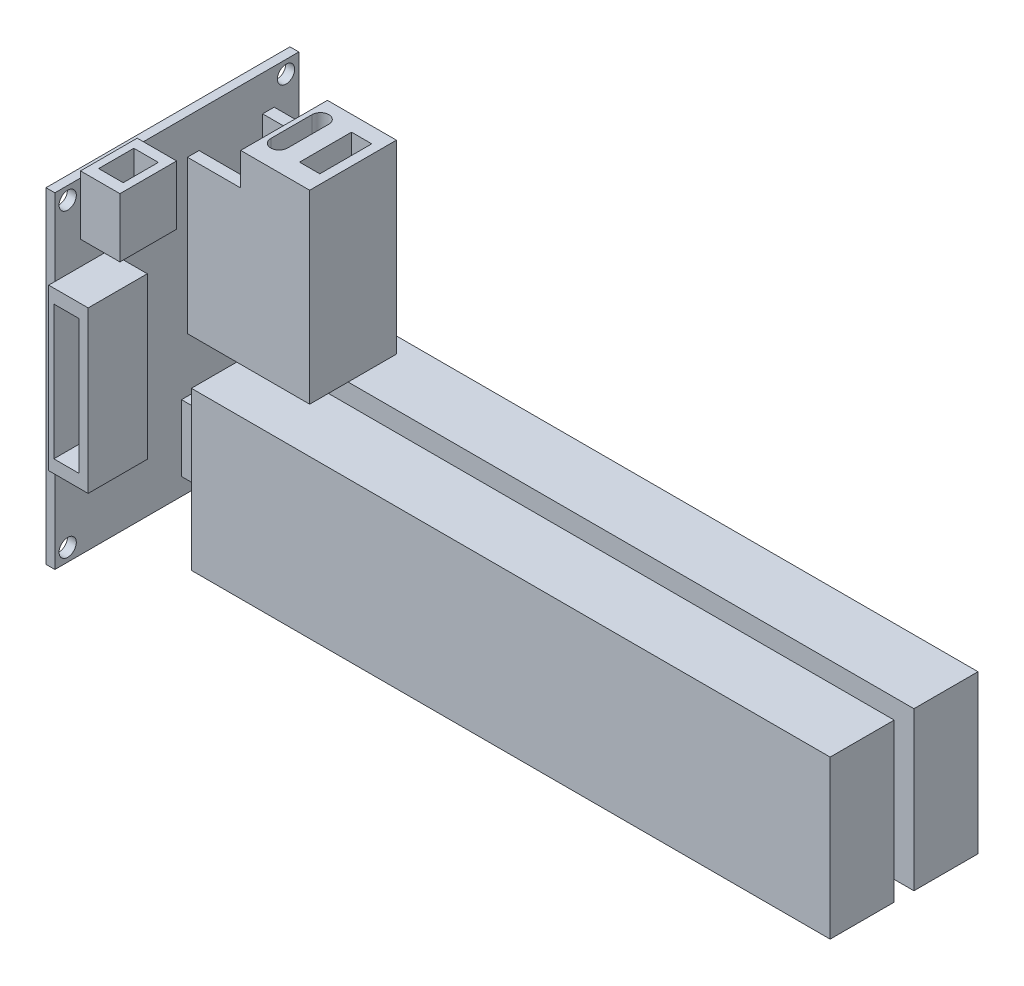
SolidWorks part; units mm, degrees
ref_plane "Płaszczyzna przednia" through (0, 0, 0) normal (0, 0, 1) x (1, 0, 0)
ref_plane "Płaszczyzna górna" through (0, 0, 0) normal (0, 1, 0) x (1, 0, 0)
ref_plane "Płaszczyzna prawa" through (0, 0, 0) normal (1, 0, 0) x (0, 0, -1)
sketch "Sketch2" plane through (0, 0, 0) normal (0, 0, 1) x (1, 0, 0)
  line L1 (0, 0) -> (129.6, 0)
  line L2 (0, 0) -> (0, 32)
  line L3 (0, 32) -> (129.6, 32)
  line L4 (129.6, 0) -> (129.6, 32)
  dimension "D1" = 32
  dimension "D2" = 129.6
extrude "Boss-Extrude1" add sketch "Sketch2" along normal blind 30
sketch "Sketch3" plane through (0, 0, 0) normal (-1, 0, 0) x (0, 0, 1)
  line L0 (0, 32) -> (0, 0) construction
  line L1 (6, 23) -> (8.4, 23)
  line L2 (6, 23) -> (6, 9.5)
  line L3 (6, 9.5) -> (8.4, 9.5)
  line L4 (8.4, 23) -> (8.4, 9.5)
  line L5 (21.6, 23) -> (24, 23)
  line L6 (21.6, 23) -> (21.6, 9.5)
  line L7 (21.6, 9.5) -> (24, 9.5)
  line L8 (24, 23) -> (24, 9.5)
  line L9 (30, 32) -> (30, 0) construction
  line L10 (30, 0) -> (0, 0) construction
  dimension "D1" = 13.5
  dimension "D2" = 2.4
  dimension "D3" = 6
  dimension "D4" = 6
  dimension "D5" = 9.5
extrude "Boss-Extrude2" add sketch "Sketch3" along normal blind 8
sketch "Sketch4" plane through (-8, 0, 0) normal (-1, 0, 0) x (0, 0, 1)
  line L1 (49.7, 6) -> (0.2, 6)
  line L2 (49.7, 6) -> (49.7, 72.2)
  line L3 (49.7, 72.2) -> (0.2, 72.2)
  line L4 (0.2, 6) -> (0.2, 72.2)
  line L5 (21.6, 9.5) -> (24, 9.5) construction
  line L6 (6, 23) -> (6, 9.5) construction
  dimension "D1" = 66.2
  dimension "D2" = 49.5
  dimension "D3" = 5.8
  dimension "D4" = 3.5
extrude "Boss-Extrude3" add sketch "Sketch4" along normal blind 1.8
sketch "Sketch5" plane through (-9.8, 0, 0) normal (-1, 0, 0) x (0, 0, 1)
  line L0 (0.2, 6) -> (49.7, 72.2) construction
  line L1 (2.8, 69.6) -> (47.1, 69.6) construction
  line L2 (2.8, 69.6) -> (2.8, 8.6) construction
  line L3 (2.8, 8.6) -> (47.1, 8.6) construction
  line L4 (47.1, 69.6) -> (47.1, 8.6) construction
  line L5 (0.2, 39.1) -> (24.95, 39.1) construction
  line L6 (0.2, 72.2) -> (0.2, 6) construction
  line L7 (2.8, 69.6) -> (47.1, 8.6) construction
  line L8 (47.1, 39.1) -> (24.95, 39.1) construction
  circle A0 centre (2.8, 69.6) radius 1.75
  circle A1 centre (47.1, 69.6) radius 1.75
  circle A2 centre (47.1, 8.6) radius 1.75
  circle A3 centre (2.8, 8.6) radius 1.75
  dimension "D1" = 2
  dimension "D3" = 3.5
  dimension "D4" = 61
  dimension "D5" = 44.3
  dimension "D2" = 2
extrude "Cut-Extrude1" cut sketch "Sketch5" against normal blind 1.8
sketch "Sketch6" plane through (-8, 0, 0) normal (1, 0, 0) x (0, 0, -1)
  line L0 (-0.2, 72.2) -> (-0.2, 6) construction
  line L1 (-5.2, 65) -> (-7.55, 65)
  line L2 (-5.2, 65) -> (-5.2, 34)
  line L3 (-5.2, 34) -> (-7.55, 34)
  line L4 (-22.8, 65) -> (-22.8, 34)
  line L5 (-49.7, 72.2) -> (-0.2, 72.2) construction
  line L6 (-20.45, 34) -> (-22.8, 34)
  line L8 (-20.45, 65) -> (-20.45, 34)
  line L10 (-7.55, 65) -> (-7.55, 34)
  line L11 (-20.45, 65) -> (-22.8, 65)
  dimension "D1" = 17.6
  dimension "D2" = 31
  dimension "D3" = 5
  dimension "D4" = 7.2
  dimension "D5" = 2.35
  dimension "D6" = 2.35
extrude "Boss-Extrude4" add sketch "Sketch6" along normal blind 10.8
sketch "Sketch7" plane through (2.8, 0, 0) normal (1, 0, 0) x (0, 0, -1)
  line L0 (-5.2, 34) -> (-5.2, 65) construction
  line L1 (-22.8, 34) -> (-5.2, 34)
  line L2 (-22.8, 34) -> (-22.8, 71.6)
  line L3 (-22.8, 71.6) -> (-5.2, 71.6)
  line L4 (-5.2, 34) -> (-5.2, 71.6)
  dimension "D1" = 37.6
extrude "Boss-Extrude5" add sketch "Sketch7" along normal blind 14
sketch "Sketch8" plane through (-8, 0, 0) normal (1, 0, 0) x (0, 0, -1)
  line L1 (-33, 73.45) -> (-44.5, 73.45)
  line L2 (-33, 73.45) -> (-33, 61.45)
  line L3 (-33, 61.45) -> (-44.5, 61.45)
  line L4 (-44.5, 73.45) -> (-44.5, 61.45)
  line L6 (-50.95, 56.6) -> (-38.95, 56.6)
  line L7 (-50.95, 56.6) -> (-50.95, 24)
  line L8 (-50.95, 24) -> (-38.95, 24)
  line L9 (-38.95, 56.6) -> (-38.95, 24)
  line L10 (-49.7, 72.2) -> (-0.2, 72.2) construction
  line L11 (-49.7, 6) -> (-49.7, 72.2) construction
  line L12 (-0.2, 72.2) -> (-0.2, 6) construction
  line L13 (-0.2, 6) -> (-49.7, 6) construction
  dimension "D1" = 11.5
  dimension "D2" = 12
  dimension "D3" = 32.6
  dimension "D4" = 12
  dimension "D5" = 1.25
  dimension "D6" = 1.25
  dimension "D7" = 44.3
  dimension "D8" = 50.6
extrude "Boss-Extrude6" add sketch "Sketch8" along normal blind 8
sketch "Sketch9" plane through (0, 71.6, 0) normal (0, 1, 0) x (1, 0, 0)
  line L0 (5.446, -9.2591) -> (5.446, -17.6324) construction
  line L1 (-6.5683, -35.1121) -> (-1.5955, -35.1121)
  line L2 (-6.5683, -35.1121) -> (-6.5683, -42.2514)
  line L3 (-6.5683, -42.2514) -> (-1.5955, -42.2514)
  line L4 (-1.5955, -35.1121) -> (-1.5955, -42.2514)
  line L5 (7.1449, -9.2591) -> (7.1449, -17.6324)
  line L6 (3.7472, -9.2591) -> (3.7472, -17.6324)
  line L8 (10.8318, -8.3496) -> (14.9435, -8.3496)
  line L9 (10.8318, -8.3496) -> (10.8318, -18.8894)
  line L10 (10.8318, -18.8894) -> (14.9435, -18.8894)
  line L11 (14.9435, -8.3496) -> (14.9435, -18.8894)
  arc A0 (7.1449, -9.2591) -> (3.7472, -9.2591) centre (5.446, -9.2591) ccw
  arc A1 (3.7472, -17.6324) -> (7.1449, -17.6324) centre (5.446, -17.6324) ccw
  point P6 (5.446, -13.4458)
extrude "Cut-Extrude2" cut sketch "Sketch9" against normal blind 8 and the other way blind 8
sketch "Sketch10" plane through (0, 0, 50.95) normal (0, 0, 1) x (1, 0, 0)
  line L1 (-6.9622, 53.8057) -> (-1.8473, 53.8057)
  line L2 (-6.9622, 53.8057) -> (-6.9622, 26.5994)
  line L3 (-6.9622, 26.5994) -> (-1.8473, 26.5994)
  line L4 (-1.8473, 53.8057) -> (-1.8473, 26.5994)
extrude "Cut-Extrude3" cut sketch "Sketch10" against normal blind 8
sketch "Sketch11" plane through (129.6, 0, 0) normal (1, 0, 0) x (0, 0, -1)
  line L0 (-30, 32) -> (0, 32) construction
  line L1 (-17, 32) -> (-13, 32)
  line L2 (-17, 32) -> (-17, 0)
  line L3 (-17, 0) -> (-13, 0)
  line L4 (-13, 32) -> (-13, 0)
  line L5 (-30, 0) -> (0, 0) construction
  line L6 (-30, 16) -> (-17, 16) construction
  line L7 (-30, 0) -> (-30, 32) construction
  line L8 (-17, 16) -> (-13, 16) construction
  line L9 (-13, 16) -> (0, 16) construction
  line L10 (0, 0) -> (0, 32) construction
  dimension "D1" = 4
extrude "Cut-Extrude4" cut sketch "Sketch11" against normal up to surface (129.6 mm away) and the other way through all up to face at (0, 16.25, 7.2)
equation "\"D4@Sketch3\"=\"D3@Sketch3\""
